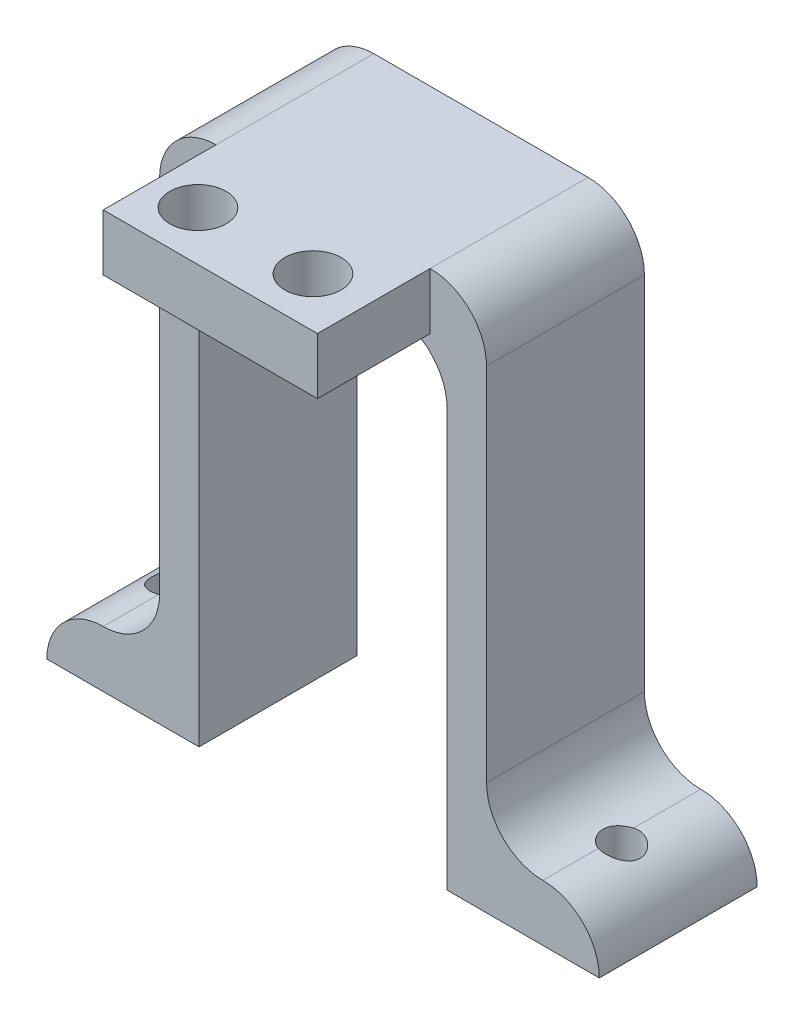
SolidWorks part; units mm, degrees
ref_plane "Front Plane" through (0, 0, 0) normal (0, 0, 1) x (1, 0, 0)
ref_plane "Top Plane" through (0, 0, 0) normal (0, 1, 0) x (1, 0, 0)
ref_plane "Right Plane" through (0, 0, 0) normal (1, 0, 0) x (0, 0, -1)
sketch "Sketch1" plane through (0, 0, 0) normal (0, 0, 1) x (1, 0, 0)
  line L0 (-24.5, 0) -> (-24.5, 5)
  line L1 (7.7, 0) -> (-7.7, 0) construction
  line L2 (-24.5, 5) -> (-14.5, 5)
  line L3 (-14.5, 5) -> (-14.5, 47)
  line L4 (-14.5, 47) -> (14.5, 47)
  line L5 (-24.5, 0) -> (-11, 0)
  line L6 (-11, 0) -> (-11, 42)
  line L7 (-11, 42) -> (11, 42)
  line L8 (0, -16.5) -> (0, 16.5) construction
  line L9 (24.5, 0) -> (11, 0)
  line L10 (24.5, 0) -> (24.5, 5)
  line L11 (24.5, 5) -> (14.5, 5)
  line L12 (11, 0) -> (11, 42)
  line L13 (14.5, 5) -> (14.5, 47)
  point P7 (0, 42)
  point P19 (0, 47)
  dimension "D1" = 22
  dimension "D2" = 5
  dimension "D4" = 5
  dimension "D6" = 42
extrude "Boss-Extrude1" add sketch "Sketch1" along normal blind 14
fillet "Fillet1" radius 5 6 edges at (-14.5, 47, 7) (14.5, 47, 7) (24.5, 5, 7) (-24.5, 5, 7) (14.5, 5, 7) (-14.5, 5, 7)
fillet "Fillet2" radius 5 2 edges at (11, 42, 7) (-11, 42, 7)
sketch "Sketch2" plane through (0, 0, 0) normal (0, 1, 0) x (1, 0, 0)
  line L0 (0, -16.5) -> (0, 16.5) construction
  circle A0 centre (-20, -7.5233) radius 1.636
  circle A1 centre (20, -7.5233) radius 1.636
  dimension "D1" = 40
extrude "Cut-Extrude3" cut sketch "Sketch2" against normal blind 10 and the other way blind 10 contours A0 | A1
sketch "Sketch4" plane through (0, 0, 14) normal (0, 0, 1) x (1, 0, 0)
  line L1 (9.5, 47) -> (-9.5, 47)
  line L2 (9.5, 47) -> (9.5, 42)
  line L3 (9.5, 42) -> (-9.5, 42)
  line L4 (-9.5, 47) -> (-9.5, 42)
extrude "Boss-Extrude2" add sketch "Sketch4" along normal blind 10
sketch "Sketch5" plane through (0, 47, 0) normal (0, 1, 0) x (1, 0, 0)
  circle A0 centre (4.7058, -19.6015) radius 2.5
  circle A1 centre (-5.4774, -19.6181) radius 2.5
  dimension "D1" = 5
  dimension "D2" = 5
extrude "Cut-Extrude4" cut sketch "Sketch5" against normal blind 10
